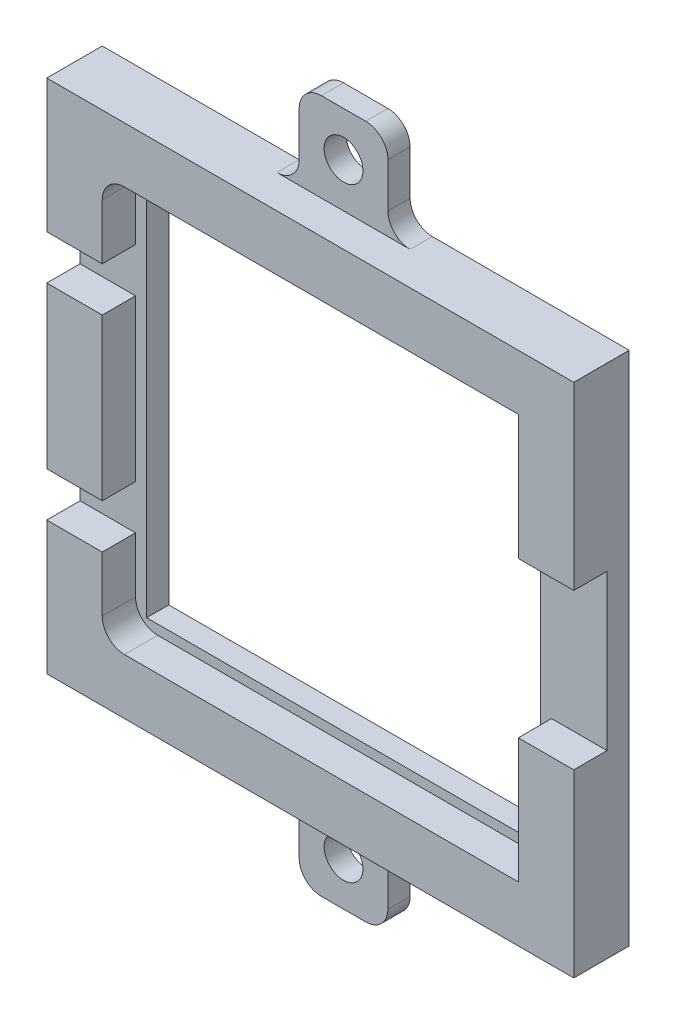
SolidWorks part; units mm, degrees
ref_plane "Front Plane" through (0, 0, 0) normal (0, 0, 1) x (1, 0, 0)
ref_plane "Top Plane" through (0, 0, 0) normal (0, 1, 0) x (1, 0, 0)
ref_plane "Right Plane" through (0, 0, 0) normal (1, 0, 0) x (0, 0, -1)
sketch "Sketch1" plane through (0, 0, 0) normal (0, 0, 1) x (1, 0, 0)
  line L1 (0, 0) -> (37.5, 0)
  line L2 (0, 0) -> (0, -36.5)
  line L3 (0, -36.5) -> (37.5, -36.5)
  line L4 (37.5, 0) -> (37.5, -36.5)
  dimension "D1" = 37.5
  dimension "D2" = 36.5
extrude "Boss-Extrude1" add sketch "Sketch1" along normal blind 5
shell "Shell1" thickness 5 removed face at (18.75, -18.25, 0) removed face at (18.75, -18.25, 5) outward yes
sketch "Sketch2" plane through (0, 0, 0) normal (0, 0, -1) x (-1, 0, 0)
  line L0 (-42.5, 5) -> (5, -41.5) construction
  line L1 (-42.5, 5) -> (5, 5)
  line L2 (-42.5, 5) -> (-42.5, -41.5)
  line L3 (-42.5, -41.5) -> (5, -41.5)
  line L4 (5, 5) -> (5, -41.5)
  line L5 (0, 0) -> (0, -36.5) construction
  line L6 (-36.5, -0.8737) -> (-1, -0.8737)
  line L7 (-36.5, -0.8737) -> (-36.5, -35.6263)
  line L8 (-36.5, -35.6263) -> (-1, -35.6263)
  line L9 (-1, -0.8737) -> (-1, -35.6263)
  line L10 (-36.5, -0.8737) -> (-1, -35.6263) construction
  line L11 (-36.5, -35.6263) -> (-1, -0.8737) construction
  line L12 (-22.75, 13) -> (-14.75, 5) construction
  line L13 (-22.75, 13) -> (-14.75, 13)
  line L14 (-22.75, 13) -> (-22.75, 5)
  line L15 (-22.75, 5) -> (-14.75, 5)
  line L16 (-14.75, 13) -> (-14.75, 5)
  line L17 (-18.75, -18.25) -> (-1, -18.25) construction
  line L18 (-22.75, -41.5) -> (-14.75, -41.5)
  line L19 (-14.75, -49.5) -> (-14.75, -41.5)
  line L20 (-22.75, -49.5) -> (-14.75, -49.5)
  line L21 (-22.75, -49.5) -> (-22.75, -41.5)
  circle A0 centre (-18.75, 9) radius 1.75
  circle A1 centre (-18.75, -45.5) radius 1.75
  point P4 (-18.75, -18.25)
  point P17 (-18.75, 5)
  line M9 (-37.5, 0) -> (0, 0)
  line M10 (0, 0) -> (0, -36.5)
  line M11 (0, -36.5) -> (-37.5, -36.5)
  line M12 (-37.5, -36.5) -> (-37.5, 0)
  line M13 (5, -41.5) -> (5, 5)
  line M14 (5, 5) -> (-42.5, 5)
  line M15 (-42.5, 5) -> (-42.5, -41.5)
  line M16 (-42.5, -41.5) -> (5, -41.5)
  dimension "D3" = 3.5
  dimension "D1" = 1
  dimension "D2" = 8
  dimension "D4" = 8
extrude "Boss-Extrude2" add sketch "Sketch2" against normal blind 2 contours L3 L1 M16 M13 M14 M15 M12 M9 M10 M11 | L6 L9 L8 L7 M9 M12 M11 M10 | L16 L13 L14 L1 A0 | L21 L20 L19 L3 A1 region at (32.625, 4.3353, 0) region at (22.6369, 9, 0) region at (18.75, -41.6131, 0) region at (18.75, -0.5233, 0)
sketch "Sketch3" plane through (0, 0, 5) normal (0, 0, 1) x (1, 0, 0)
  line L0 (-5, 5) -> (-5, -41.5) construction
  line L5 (0, 0) -> (0, -36.5) construction
  line L7 (-5, -25.5) -> (0, -25.5)
  line L8 (-5, -25.5) -> (-5, -29.5)
  line L9 (-5, -29.5) -> (0, -29.5)
  line L10 (0, -25.5) -> (0, -29.5)
  line L11 (37.5, -11.25) -> (42.5, -11.25)
  line L12 (37.5, -11.25) -> (37.5, -25.25)
  line L13 (37.5, -25.25) -> (42.5, -25.25)
  line L14 (42.5, -11.25) -> (42.5, -25.25)
  line L15 (42.5, -41.5) -> (42.5, 5) construction
  line L16 (1, -18.25) -> (37.5, -18.25) construction
  line L18 (-5, -7) -> (0, -7)
  line L19 (0, -11) -> (0, -7)
  line L20 (-5, -11) -> (0, -11)
  line L21 (-5, -11) -> (-5, -7)
  line L22 (1, -0.8737) -> (1, -35.6263) construction
  line L23 (37.5, -36.5) -> (37.5, 0) construction
  point P16 (34.3761, -18.75)
  point P19 (0, 0)
  point P24 (3.2736, -18.75)
  line M14 (0, -36.5) -> (0, 0)
  line M16 (37.5, 0) -> (37.5, -36.5)
  line M18 (-5, 5) -> (-5, -41.5)
  line M20 (42.5, -41.5) -> (42.5, 5)
  dimension "D1" = 14
  dimension "D2" = 16
  dimension "D3" = 4
extrude "Cut-Extrude2" cut sketch "Sketch3" against normal up to vertex (3 mm away) contours L20 L18 M18 M14 | L9 L7 M18 M14 | L12 L13 L11 M16 M20 region at (-2.5, -27.5, 5) region at (-2.5, -9, 5) region at (40, -18.25, 5) up to point (0, 0, 2)
fillet "Fillet1" radius 2 10 edges at (14.75, 13, 1) (22.75, 13, 1) (22.75, 5, 1) (14.75, 5, 1) (0, 0, 3.5) (0, -36.5, 3.5) (22.75, -49.5, 1) (14.75, -49.5, 1) (14.75, -41.5, 1) (22.75, -41.5, 1)
